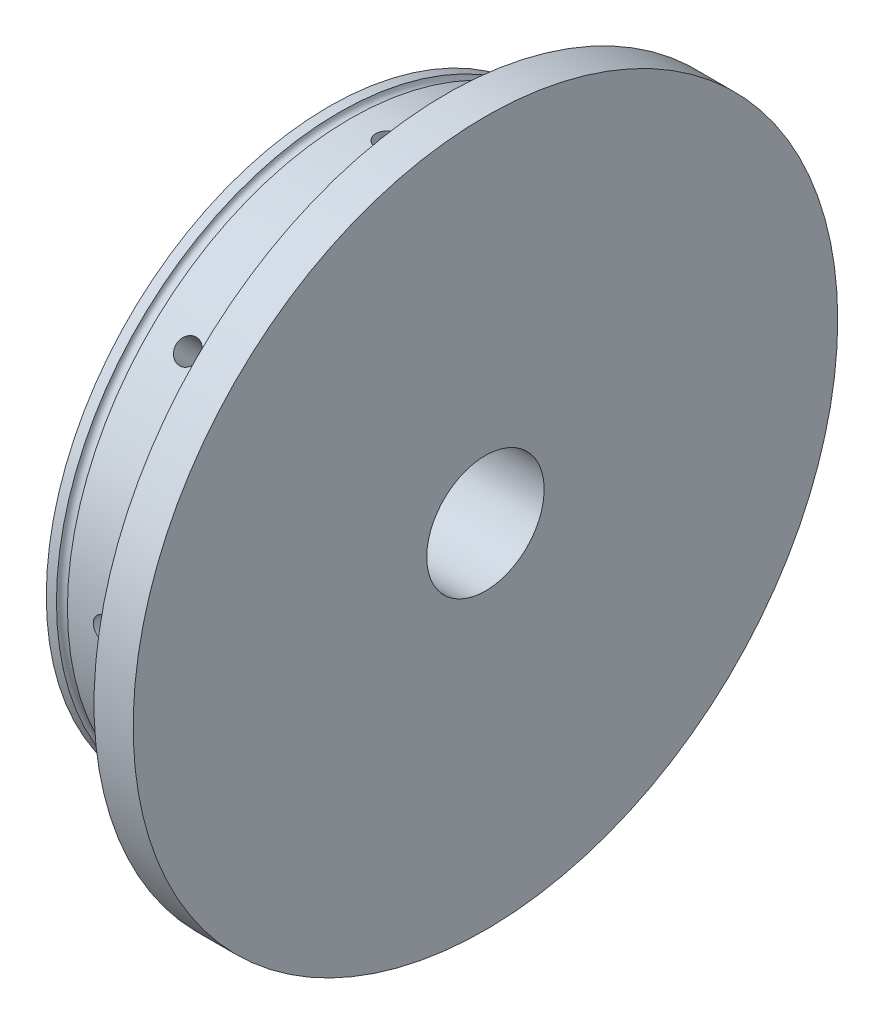
SolidWorks part; units mm, degrees
material "7075-T6 (SN)"
ref_plane "Front Plane" through (0, 0, 0) normal (0, 0, 1) x (1, 0, 0)
ref_plane "Top Plane" through (0, 0, 0) normal (0, 1, 0) x (1, 0, 0)
ref_plane "Right Plane" through (0, 0, 0) normal (1, 0, 0) x (0, 0, -1)
sketch "Sketch1" plane through (0, 0, 0) normal (1, 0, 0) x (0, 0, -1)
  circle A0 centre (0, 0) radius 57.15
  dimension "D1" = 114.3
extrude "Boss-Extrude1" add sketch "Sketch1" along normal blind 6.35
sketch "Sketch2" plane through (0, 0, 0) normal (-1, 0, 0) x (0, 0, 1)
  circle A0 centre (0, 0) radius 45.847
  dimension "D1" = 91.694
extrude "Boss-Extrude2" add sketch "Sketch2" along normal blind 19.05
sketch "Sketch3" plane through (-19.05, 0, 0) normal (-1, 0, 0) x (0, 0, 1)
  circle A0 centre (0, 0) radius 34.925
  dimension "D1" = 69.85
extrude "Cut-Extrude1" cut sketch "Sketch3" against normal blind 3.175
sketch "Sketch4" plane through (-15.875, 0, 0) normal (-1, 0, 0) x (0, 0, 1)
  circle A0 centre (0, 0) radius 9.525
  dimension "D1" = 19.05
extrude "Cut-Extrude2" cut sketch "Sketch4" against normal through all
sketch "Sketch5" plane through (0, 0, 0) normal (0, 0, 1) x (1, 0, 0)
  line L0 (0, 45.847) -> (-19.05, 45.847) construction
  line L1 (-19.05, 45.847) -> (-19.05, -45.847) construction
  line L2 (0, 0) -> (-28.6633, 0) construction
  circle A0 centre (-16.51, 45.847) radius 0.889
  dimension "D1" = 1.778
  dimension "D2" = 2.54
revolve "Cut-Revolve1" cut sketch "Sketch5" angle 360 about L2
ref_plane "Plane1" through (0, 0, 45.847) normal (0, 0, 1) x (1, 0, 0)
sketch "Sketch6" plane through (0, 0, 45.847) normal (0, 0, 1) x (1, 0, 0)
  line L0 (0, 45.847) -> (0, -45.847) construction
  circle A0 centre (-9.525, 0) radius 1.905
  dimension "D1" = 3.81
  dimension "D2" = 9.525
extrude "Cut-Extrude3" cut sketch "Sketch6" against normal blind 6.35
pattern_circular "CirPattern1" count 8 every 45 about axis through (-19.05, 0, 0) along (1, 0, 0) of "Cut-Extrude3"
